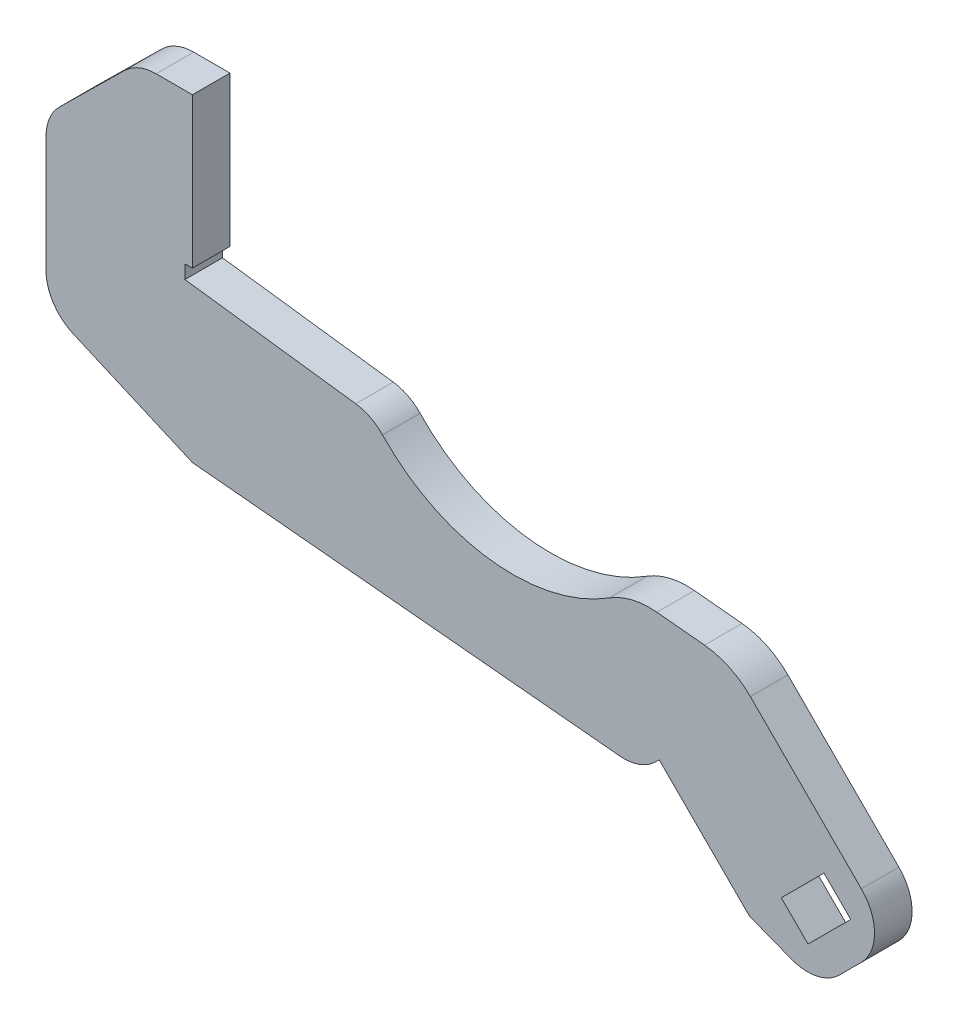
SolidWorks part; units mm, degrees
material "PBT General Purpose"
ref_plane "Front Plane" through (0, 0, 0) normal (0, 0, 1) x (1, 0, 0)
ref_plane "Top Plane" through (0, 0, 0) normal (0, 1, 0) x (1, 0, 0)
ref_plane "Right Plane" through (0, 0, 0) normal (1, 0, 0) x (0, 0, -1)
sketch "frame_outline" plane through (0, 0, 0) normal (0, 0, 1) x (1, 0, 0)
  line L0 (0, 0) -> (0, -0.6) construction
  line L1 (0, 0) -> (0.3, 0) construction
  line L2 (0, -0.6) -> (-0.05, -0.6) construction
  line L3 (0, 0) -> (4.9667, -4.9667) construction
  line L63 (-0.05, -0.6) -> (-0.05, -1.6)
  line L64 (-0.05, -0.6) -> (-0.4144, -0.6)
  line L65 (-0.4144, -0.6) -> (-1.025, -1.2016)
  line L66 (-1.025, -1.2016) -> (-1.025, -2.2972)
  line L67 (-1.025, -2.2972) -> (-0.05, -2.7212)
  line L71 (-0.05, -2.7212) -> (2.9356, -3.0041)
  line L72 (2.9356, -3.0041) -> (3.0582, -2.8815)
  line L73 (3.0582, -2.8815) -> (3.6593, -3.4825)
  line L74 (3.6593, -3.4825) -> (4.1203, -3.6607)
  line L75 (4.1203, -3.6607) -> (4.6167, -3.1643)
  line L76 (4.6167, -3.1643) -> (3.5388, -2.0864)
  line L77 (3.5388, -2.0864) -> (2.8549, -2.0196)
  line L78 (-0.1, -1.6906) -> (-0.1, -1.6)
  line L79 (-0.1, -1.6) -> (-0.05, -1.6)
  line L80 (3.8714, -3.2704) -> (4.0496, -3.4486)
  line L81 (3.8714, -3.2704) -> (4.1557, -2.9861)
  line L82 (4.0496, -3.4486) -> (4.3339, -3.1643)
  line L83 (4.1557, -2.9861) -> (4.3339, -3.1643)
  line L84 (0, -0.6) -> (0, -4.6335) construction
  line L85 (3.6593, -3.4825) -> (3.8714, -3.2704) construction
  line L86 (1.1495, -1.8531) -> (-0.1, -1.6906)
  arc A0 (1.1495, -1.8531) -> (2.8549, -2.0196) centre (2.0839, -1.1001) ccw
  point P25 (0, -2.3724)
  dimension "D2" = 0.3
  dimension "D3" = 0.6
  dimension "D8" = 1
  dimension "D4" = 45
  dimension "D1" = 0.05
  dimension "D5" = 0.125
  dimension "D7" = 0.05
  dimension "D10" = 0.85
  dimension "D11" = 0.252
  dimension "D12" = 0.402
  dimension "D13" = 0.3
  dimension "D14" = 0.2
  dimension "D15" = 0.2
  dimension "D16" = 0.1
  dimension "D17" = 4.2
extrude "Boss-Extrude1" add sketch "frame_outline" along normal mid plane 0.25
fillet "Fillet1" radius 0.3 7 edges at (4.6167, -3.1643, 0) (4.1203, -3.6607, 0) (1.1495, -1.8531, 0) (-0.4144, -0.6, 0) (-1.025, -1.2016, 0) (-1.025, -2.2972, 0) (2.9356, -3.0041, 0)
fillet "Fillet2" radius 0.5 2 edges at (3.5388, -2.0864, 0) (2.8549, -2.0196, 0)
equation "\"t\"= 0.25'thickness of the sheets"
equation "\"t_cf\"= 0.115'thickness of single carbon fiber layer"
equation "\"t_kapton\"= 0.025'thickness of single Kapton flex layer"
equation "\"t_fr4\"= 0.1'thickness of FR4 with copper layer"
equation "\"joint_flex\"= 0.1'Width of flextures gap"
equation "\"joint_flex_eff\"= 0.02'Width of flecture after castelation"
equation "\"joint_fold\"= 0.2'Width of folding joints for 90deg fold"
equation "\"gap_tolerance\"= 0.002'Width to have interfecence fit between carbon fiber inserts"
equation "\"assemble_angle\"= 90'Angle of assembly parts"
equation "\"D1@Boss-Extrude1\"=\"t\""
equation "\"link_lift\"= 0.5'Actuation linkage amplification for the lift motion"
equation "\"link_swing\"= 0.45'Actuation linkage amplification for the swing motion"
equation "\"D1@frame_outline\"=\"joint_flex\"/2"
equation "\"D5@frame_outline\"=\"t\"/2"
equation "\"D11@frame_outline\"=\"t\"+\"gap_tolerance\""
equation "\"D12@frame_outline\"=0.4+\"gap_tolerance\""
equation "\"D10@frame_outline\"=0.80mm+0.05"
